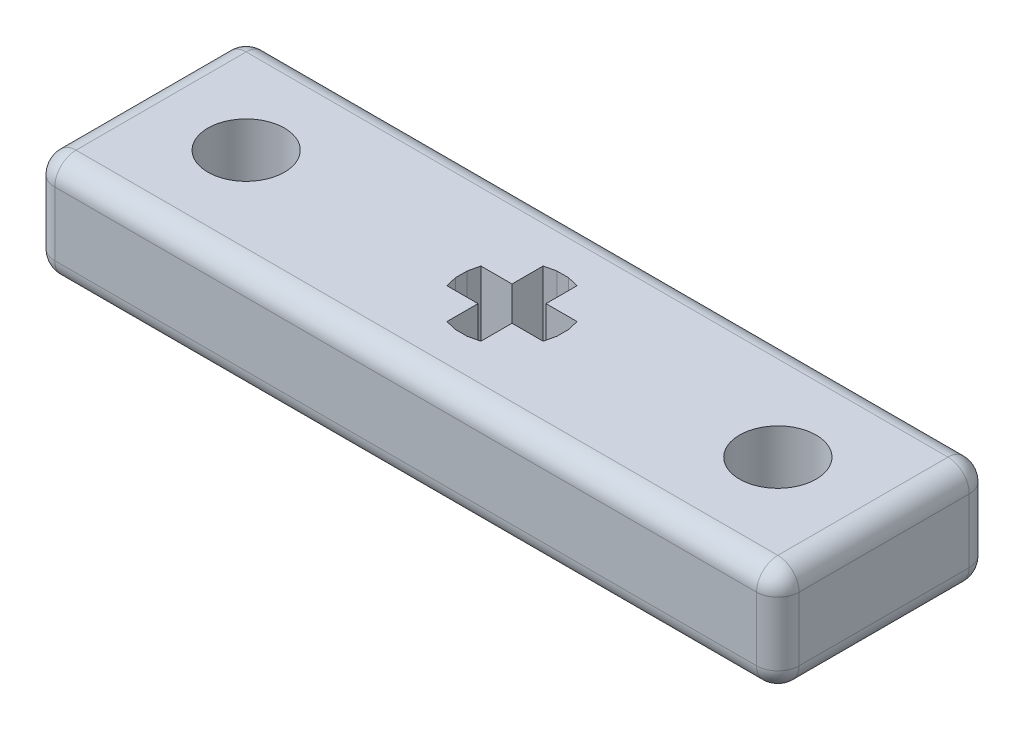
SolidWorks part; units mm, degrees
ref_plane "Front Plane" through (0, 0, 0) normal (0, 0, 1) x (1, 0, 0)
ref_plane "Top Plane" through (0, 0, 0) normal (0, 1, 0) x (1, 0, 0)
ref_plane "Right Plane" through (0, 0, 0) normal (1, 0, 0) x (0, 0, -1)
sketch "Sketch1" plane through (0, 0, 0) normal (0, 1, 0) x (1, 0, 0)
  line L0 (-0.8, 0.8) -> (-0.8, 2.2627)
  line L1 (-17.5, -5) -> (17.5, -5)
  line L2 (-17.5, -5) -> (-17.5, 5)
  line L3 (-17.5, 5) -> (17.5, 5)
  line L4 (17.5, -5) -> (17.5, 5)
  line L5 (-17.5, -5) -> (17.5, 5) construction
  line L6 (-17.5, 5) -> (17.5, -5) construction
  line L8 (-5, -5) -> (-5, 5)
  line L10 (5, -5) -> (5, 5)
  line L11 (-1.4213, -5) -> (1.4358, 5) construction
  line L12 (-1.4358, 5) -> (1.4213, -5) construction
  line L13 (-0.8, 2.2627) -> (-0.2701, 2.3847)
  line L14 (-0.2701, 2.3847) -> (0.2701, 2.3847)
  line L15 (0.2701, 2.3847) -> (0.8, 2.2627)
  line L16 (0.8, 2.2627) -> (0.8, 0.8)
  line L17 (0.8, 0.8) -> (2.2627, 0.8)
  line L18 (2.2627, 0.8) -> (2.3847, 0.2701)
  line L19 (2.3847, 0.2701) -> (2.3847, -0.2701)
  line L20 (2.3847, -0.2701) -> (2.2627, -0.8)
  line L21 (2.2627, -0.8) -> (0.8, -0.8)
  line L22 (0.8, -0.8) -> (0.8, -2.2627)
  line L23 (0.8, -2.2627) -> (0.2701, -2.3847)
  line L24 (0.2701, -2.3847) -> (-0.2701, -2.3847)
  line L25 (-0.2701, -2.3847) -> (-0.8, -2.2627)
  line L26 (-0.8, -2.2627) -> (-0.8, -0.8)
  line L27 (-0.8, -0.8) -> (-2.2627, -0.8)
  line L28 (-2.2627, -0.8) -> (-2.3847, -0.2701)
  line L29 (-2.3847, -0.2701) -> (-2.3847, 0.2701)
  line L30 (-2.3847, 0.2701) -> (-2.2627, 0.8)
  line L31 (-2.2627, 0.8) -> (-0.8, 0.8)
  line L32 (-5, 5) -> (5, 5) construction
  circle A1 centre (0, 0) radius 3
  point P2 (0, 5)
  dimension "D1" = 6
  dimension "D3" = 10
  dimension "D4" = 35
  dimension "D5" = 10
extrude "Boss-Extrude1" add sketch "Sketch1" along normal blind 5 contours L1 L10 L3 L8 | L3 L10 L8 | L1 L8 L3 L2 | L10 L1 L8 | L2 L1 L4 L3 | L0 L13 L14 L15 L16 L17 L18 L19 L20 L21 L22 L23 L24 L25 L26 L27 L28 L29 L30 L31 region at (-11.25, 0, 0) region at (-4.8586, 0, 0)
fillet "Fillet4" radius 1 4 edges at (17.5, 2.5, -5) (17.5, 2.5, 5) (-17.5, 2.5, 5) (-17.5, 2.5, -5)
hole_wizard "M3 Clearance Hole1" positions "Sketch2" profile "Sketch3" hole size "M3" standard "ANSI Metric" end condition through all
sketch "Sketch2" plane through (0, 0, 0) normal (0, 1, 0) x (1, 0, 0)
  line L0 (-12.5, 0) -> (12.5, 0)
  line L2 (17.5, -4) -> (17.5, 4) construction
  point P0 (-12.5, 0)
  point P2 (12.5, 0)
  point P21 (0, 0)
  point P24 (0, 0)
  point P26 (0, 0)
  dimension "D1" = 5
sketch "Sketch3" plane through (-12.5, 0, 0) normal (1, 0, 0) x (0, 0, -1)
  line L0 (0, 0) -> (0, 5)
  line L1 (0, 5) -> (1.8, 5)
  line L2 (1.8, 5) -> (1.8, 0)
  line L5 (1.8, 0) -> (0, 0)
  line L11 (0, -6.35) -> (0, 107.95) construction
  dimension "Thru Hole Dia." = 3.6
  dimension "Thru Hole Depth" = 5
fillet "Fillet6" radius 1 16 edges at (-17.2071, 5, 4.7071) (0, 5, 5) (17.2071, 5, 4.7071) (17.2071, 5, -4.7071) (0, 5, -5) (-17.2071, 5, -4.7071) (-17.2071, 0, 4.7071) (0, 0, 5) (17.2071, 0, 4.7071) (17.2071, 0, -4.7071) (0, 0, -5) (-17.2071, 0, -4.7071) (17.5, 5, 0) (17.5, 0, 0) (-17.5, 5, 0) (-17.5, 0, 0)
